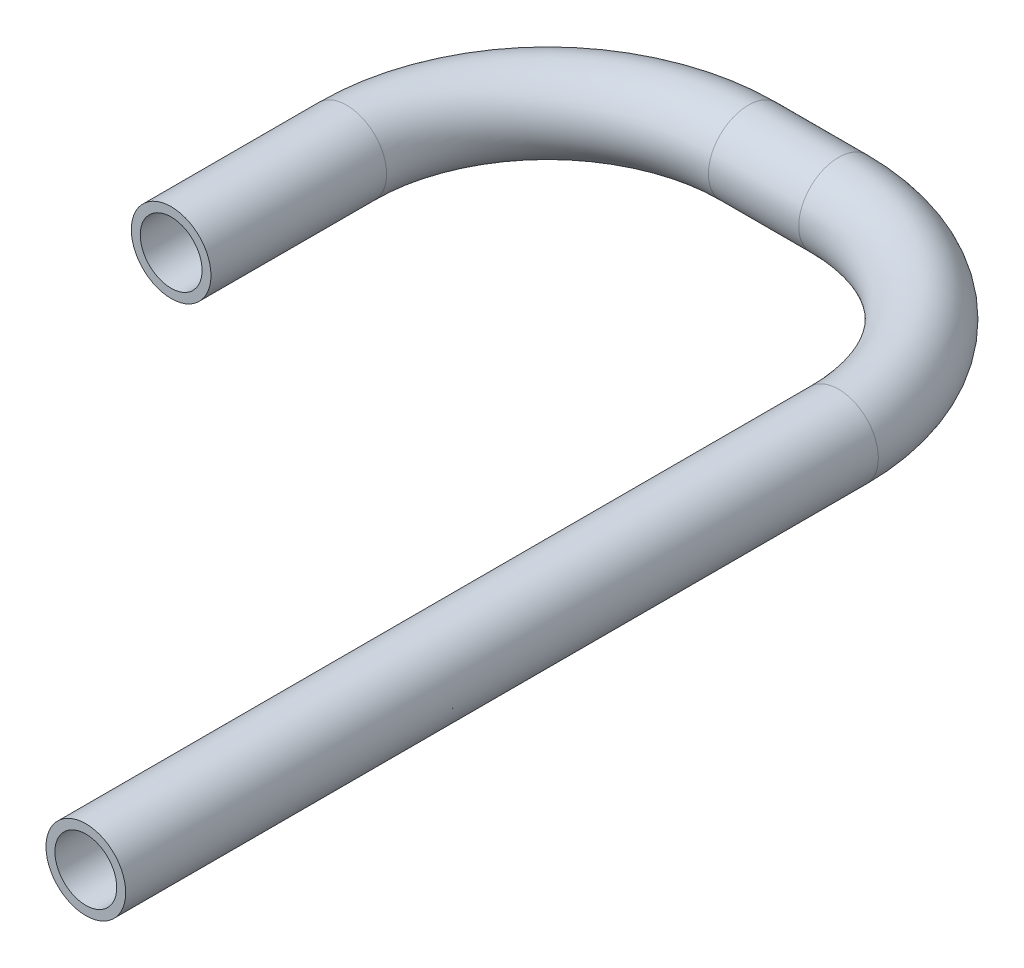
SolidWorks part; units mm, degrees
ref_plane "Front Plane" through (0, 0, 0) normal (0, 0, 1) x (1, 0, 0)
ref_plane "Top Plane" through (0, 0, 0) normal (0, 1, 0) x (1, 0, 0)
ref_plane "Right Plane" through (0, 0, 0) normal (1, 0, 0) x (0, 0, -1)
sketch "Sketch1" plane through (0, 0, 0) normal (0, 1, 0) x (1, 0, 0)
  line L0 (0, 0) -> (0, 14)
  line L1 (16, 30) -> (23.2, 30)
  line L2 (39.2, 14) -> (39.2, -46)
  arc A0 (23.2, 30) -> (39.2, 14) centre (23.2, 14) cw
  arc A1 (0, 14) -> (16, 30) centre (16, 14) cw
  dimension "D1" = 16
  dimension "D2" = 16
  dimension "D3" = 14
  dimension "D4" = 60
  dimension "D5" = 39.2
sketch "Sketch2" plane through (0, 0, 0) normal (0, 0, 1) x (1, 0, 0)
  circle A0 centre (0, 0) radius 3.175
  dimension "D1" = 6.35
sweep "Sweep-Thin1" add profiles "Sketch2" path "Sketch1" parameters "D1"=0.7112
